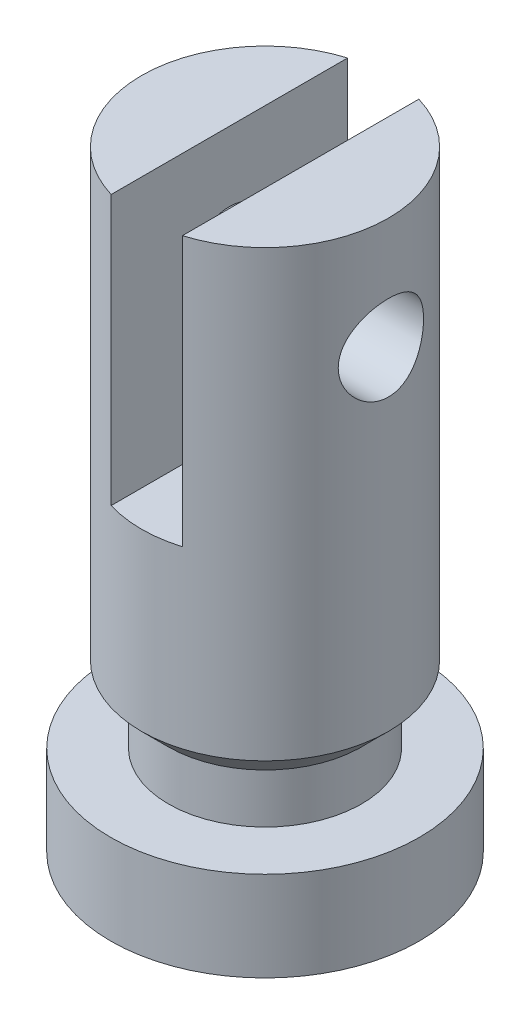
SolidWorks part; units mm, degrees
material "ABS"
ref_plane "Front Plane" through (0, 0, 0) normal (0, 0, 1) x (1, 0, 0)
ref_plane "Top Plane" through (0, 0, 0) normal (0, 1, 0) x (1, 0, 0)
ref_plane "Right Plane" through (0, 0, 0) normal (1, 0, 0) x (0, 0, -1)
sketch "Sketch1" plane through (0, 0, 0) normal (0, 1, 0) x (1, 0, 0)
  circle A0 centre (0, 0) radius 6.875
  dimension "D1" = 13.75
extrude "Boss-Extrude1" add sketch "Sketch1" along normal blind 4
sketch "Sketch8" plane through (0, 4, 0) normal (0, 1, 0) x (1, 0, 0)
  circle A0 centre (0, 0) radius 4.3
  dimension "D1" = 8.6
extrude "Boss-Extrude4" add sketch "Sketch8" along normal blind 2.2
sketch "Sketch2" plane through (0, 6.2, 0) normal (0, 1, 0) x (1, 0, 0)
  circle A2 centre (0, 0) radius 5.5
  point P0 (0, 0)
  dimension "D1" = 11
extrude "Boss-Extrude2" add sketch "Sketch2" along normal blind 9
sketch "Sketch3" plane through (0, 15.2, 0) normal (0, 1, 0) x (1, 0, 0)
  circle A2 centre (0, 0) radius 5.5 construction
  circle A3 centre (0, 0) radius 5.5
extrude "Boss-Extrude3" add sketch "Sketch3" along normal blind 12
sketch "Sketch4" plane through (0, 27.2, 0) normal (0, 1, 0) x (1, 0, 0)
  line L1 (-1.5875, 5.5) -> (1.5875, 5.5)
  line L2 (-1.5875, 5.5) -> (-1.5875, -5.5)
  line L3 (-1.5875, -5.5) -> (1.5875, -5.5)
  line L4 (1.5875, 5.5) -> (1.5875, -5.5)
  line L5 (-1.5875, 5.5) -> (1.5875, -5.5) construction
  line L6 (-1.5875, -5.5) -> (1.5875, 5.5) construction
  circle A1 centre (0, 0) radius 5.5
  circle A2 centre (0, 0) radius 5.5 construction
  point P0 (0, 0)
  dimension "D2" = 3.175
extrude "Cut-Extrude1" cut sketch "Sketch4" against normal blind 12
sketch "Sketch5" plane through (1.5875, 0, 0) normal (-1, 0, 0) x (0, 0, 1)
  line L0 (5.2659, 15.2) -> (-5.2659, 15.2) construction
  line L1 (5.2659, 27.2) -> (-5.2659, 27.2) construction
  line L2 (5.2659, 15.2) -> (-5.2659, 15.2)
  line L3 (5.2659, 27.2) -> (-5.2659, 27.2)
  line L4 (0, 15.2) -> (0, 22.2) construction
  circle A0 centre (0, 22.2) radius 1.9
  dimension "D2" = 3.8
  dimension "D1" = 7
extrude "Cut-Extrude2" cut sketch "Sketch5" against normal through all both and the other way through all contours A0
chamfer "Chamfer1" distance 1.2 angle 45 1 edges at (0, 6.2, 5.5)
equation "\"prop-dist\"= 80mm"
equation "\"prop-hole-depth\"= 9mm"
equation "\"prop-hole-diameter\"= 11mm"
equation "\"rivet-extension\"= 12mm"
equation "\"rivet-hole-extension\"= 7mm"
equation "\"rivet-hole-diameter\"= 3.8mm"
equation "\"ski-length\"= 100mm"
equation "\"th\"= 0.125in'material thickness"
equation "\"ski-height\"= 30mm"
equation "\"ski-curve-gap\"= 60mm"
equation "\"ski-curve-height\"= \"rivet-hole-extension\""
equation "\"min-width\"= 4mm"
equation "\"prop-hole-diameter-small\"= 8.6mm"
equation "\"D1@Sketch1\"=\"prop-hole-diameter\"*1.25"
equation "\"D1@Sketch2\"=\"prop-hole-diameter\""
equation "\"D1@Boss-Extrude2\"=\"prop-hole-depth\""
equation "\"D1@Boss-Extrude3\"=\"rivet-extension\""
equation "\"D2@Sketch4\"=\"th\""
equation "\"D1@Cut-Extrude1\"=\"rivet-extension\""
equation "\"D1@Sketch5\"=\"rivet-hole-extension\""
equation "\"D2@Sketch5\"=\"rivet-hole-diameter\""
equation "\"D1@Sketch8\"=\"prop-hole-diameter-small\""
equation "\"D1@Chamfer1\"=(\"prop-hole-diameter\"-\"prop-hole-diameter-small\")/2"
equation "\"prop-dist-width\"= 86.5mm"
equation "\"prop-dist-length\"= 80mm"
equation "\"prop-boost\"= 4.4mm"
equation "\"back-drop\"= 5mm"
equation "\"T\"= 0.125in'Material Thickness"
equation "\"tof_c2c\"= 19.9mm'Center to center distance of TOF sensor holes"
equation "\"tof_d\"= 3mm'TOF hole diameter"
equation "\"tof_w\"= 12.6mm'TOF width"
equation "\"tof_l\"= 15.6mm'TOF length"
equation "\"pin_w\"= 2.3mm'A standard IO Pin socket width"
equation "\"pin_l\"= 2.5mm'A standard IO Pin socket length"
equation "\"esp_pin_num\"= 8'Number of pins on one side of the ESP"
equation "\"esp_l\"= 40mm'ESP length"
equation "\"esp_w\"= 27mm'ESP width"
equation "\"esp_pin_inset\"= 3mm'Distance that ESP pins are inset"
equation "\"bat_l\"= 27mm'Battery length"
equation "\"bat_w\"= 20mm'Battery width"
equation "\"bat_h\"= 6mm'Battery thickness"
equation "\"boost_w\"= 17.2mm"
equation "\"boost_l\"= 37mm"
equation "\"boost_hole_inset\"= 2.2mm"
equation "\"boost_hole_dist\"= 7mm"
equation "\"boost_hole_d\"= 2mm"
